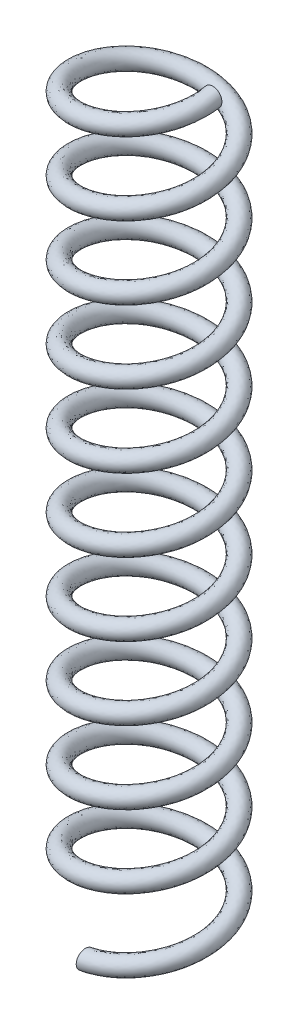
SolidWorks part; units mm, degrees
note: '?' marks a value the reader was unsure of.
material "AISI 304"
ref_plane "Front Plane" through (0, 0, 0) normal (0, 0, 1) x (1, 0, 0)
ref_plane "Top Plane" through (0, 0, 0) normal (0, 1, 0) x (1, 0, 0)
ref_plane "Right Plane" through (0, 0, 0) normal (1, 0, 0) x (0, 0, -1)
ref_axis "SpringAxis" through (0, 1.15, 0) along (0, -1, 0)?
sketch "SpringBodyDiameterS" plane through (0, 0, 0) normal (0, 0, 1) x (1, 0, 0)
  line L0 (0, 0) -> (1.5, 0) construction
  line L1 (0, 0) -> (0, 1) construction
  line L2 (1.75, 0) -> (2, 0) construction
  circle A0 centre (1.75, 0) radius 0.25
  dimension "WireDia" = 0.5
  dimension "RefRevolve" = 1
  dimension "RevolveDia" = 3.5
  dimension "RefID" = 1.5
  dimension "RefOD" = 2
sketch "SpringHelixS" plane through (0, 0, 0) normal (0, 1, 0) x (1, 0, 0)
  circle A0 centre (0, 0) radius 1.75
  dimension "RefDia" = 3.5
curve "SPRING HELIX" pitch 2 height 20.5 turns 10.25 parameters "Height"=20.5, "Pitch"=2
sweep "SPRING" add profiles "SpringBodyDiameterS" path "SPRING HELIX"
